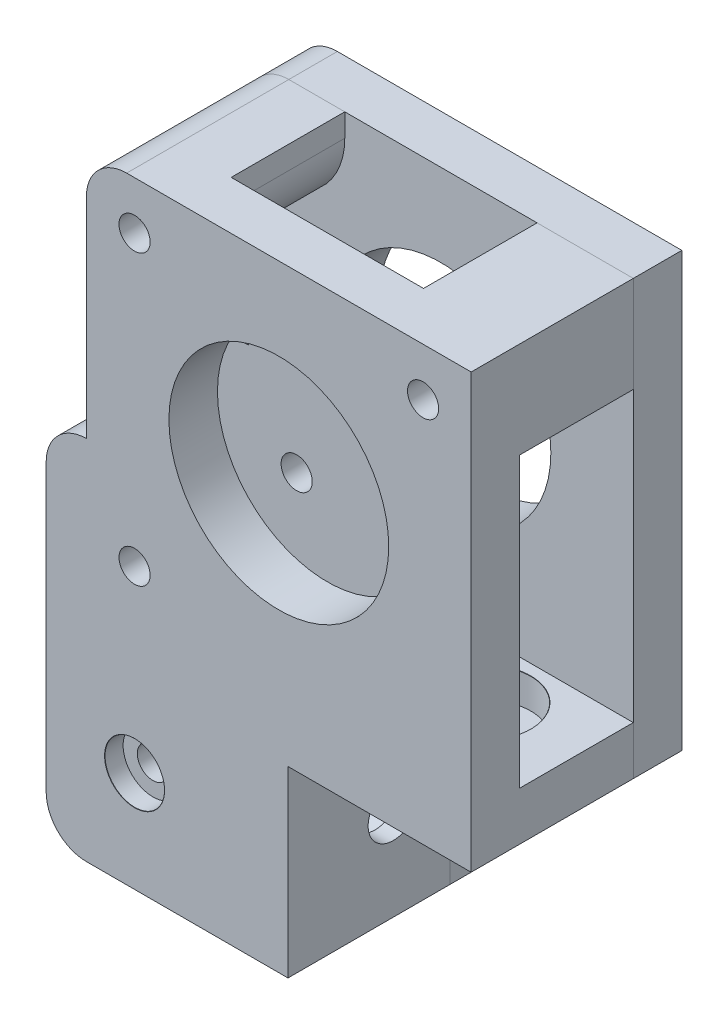
SolidWorks part; units mm, degrees
ref_plane "Front Plane" through (0, 0, 0) normal (0, 0, 1) x (1, 0, 0)
ref_plane "Top Plane" through (0, 0, 0) normal (0, 1, 0) x (1, 0, 0)
ref_plane "Right Plane" through (0, 0, 0) normal (1, 0, 0) x (0, 0, -1)
sketch "Sketch16" plane through (0, 0, 0) normal (0, 0, 1) x (1, 0, 0)
  line L1 (-21, 21) -> (21, 21)
  line L2 (-21, 21) -> (-21, -21)
  line L3 (-21, -21) -> (21, -21)
  line L4 (21, 21) -> (21, -21)
  line L5 (-21, 21) -> (21, -21) construction
  line L6 (-21, -21) -> (21, 21) construction
  point P0 (0, 0)
  dimension "D1" = 42
  dimension "D2" = 42
extrude "Boss-Extrude4" add sketch "Sketch16" against normal blind 5.3
sketch "Sketch19" plane through (0, 0, 0) normal (0, 0, 1) x (1, 0, 0)
  line L0 (21, -21) -> (21, -26.3)
  line L1 (21, -26.3) -> (1, -26.3)
  line L2 (1, -26.3) -> (1, -21)
  line L3 (-21, -21) -> (21, -21) construction
  line L4 (1, -21) -> (21, -21)
  dimension "D1" = 5.3
  dimension "D2" = 20
extrude "Boss-Extrude7" add sketch "Sketch19" against normal blind 23
sketch "Sketch20" plane through (0, 0, 0) normal (0, 0, 1) x (1, 0, 0)
  line L0 (1, -21) -> (-4.3, -21)
  line L1 (-21, -21) -> (1, -21) construction
  line L2 (-4.3, -21) -> (-4.3, -46.3)
  line L3 (-4.3, -46.3) -> (1, -46.3)
  line L4 (1, -46.3) -> (1, -21)
  dimension "D1" = 25.3
  dimension "D2" = 5.3
extrude "Boss-Extrude8" add sketch "Sketch20" against normal blind 23
sketch "Sketch21" plane through (0, -21, 0) normal (0, -1, 0) x (1, 0, 0)
  line L1 (-21, -5.3) -> (-4.3, -5.3)
  line L2 (-21, -5.3) -> (-21, 0)
  line L3 (-21, 0) -> (-4.3, 0)
  line L4 (-4.3, -5.3) -> (-4.3, 0)
extrude "Boss-Extrude9" add sketch "Sketch21" along normal up to surface (25.3 mm away) up to face at (-1.65, -46.3, -11.5)
sketch "Sketch22" plane through (0, 0, -23) normal (0, 0, -1) x (-1, 0, 0)
  line L0 (-21, -21) -> (-21, 21)
  line L1 (-21, 21) -> (21, 21)
  line L2 (21, 21) -> (21, -46.3)
  line L3 (21, -46.3) -> (4.3, -46.3)
  line L4 (4.3, -46.3) -> (4.3, -21)
  line L5 (4.3, -21) -> (-21, -21)
extrude "Boss-Extrude10" add sketch "Sketch22" against normal blind 5.3
sketch "Sketch23" plane through (-4.3, 0, 0) normal (-1, 0, 0) x (0, 0, 1)
  line L0 (-5.3, -46.3) -> (-5.3, -21) construction
  line L1 (-17.7, -46.3) -> (-5.3, -46.3) construction
  point P0 (-11.5, -36.3)
  dimension "D1" = 6.2
  dimension "D2" = 10
sketch "Sketch24" plane through (0, -21, 0) normal (0, 1, 0) x (1, 0, 0)
  line L0 (-21, 17.7) -> (21, 17.7) construction
  line L1 (21, 17.7) -> (21, 5.3) construction
  point P0 (11, 11.5)
  dimension "D1" = 6.2
  dimension "D2" = 10
hole_wizard "CBORE for M5 Cheese Head Screw1" positions "3DSketch1" profile "Sketch25" counterbore size "M5" standard "ISO" end condition up to next
sketch3d "3DSketch1"
  point P0 (11, -21, -11.5)
  point P3 (-4.3, -36.3, -11.5)
sketch "Sketch25" plane through (11, -21, -11.5) normal (1, 0, 0) x (0, 0, 1)
  line L0 (0, 0) -> (0, 5.3)
  line L1 (0, 5.3) -> (2.75, 5.3)
  line L3 (2.75, 5.3) -> (2.75, 3.3)
  line L4 (5, 3.3) -> (2.75, 3.3)
  line L5 (5, 3.3) -> (5, 0.025)
  line L6 (5, 0.025) -> (5.025, 0)
  line L7 (5.025, 0) -> (0, 0)
  line L8 (-5, 0.025) -> (-5.025, 0) construction
  line L11 (0, -6.35) -> (0, 107.95) construction
  dimension "Thru Hole Dia." = 5.5
  dimension "Thru Hole Depth" = 5.3
  dimension "C'Bore Dia." = 10
  dimension "C'Bore Depth" = 3.3
  dimension "Near C'Sink Dia." = 10.05
  dimension "Near C'Sink Angle" = 90
sketch "Sketch27" plane through (0, 0, -5.3) normal (0, 0, -1) x (-1, 0, 0)
  line L1 (10.5, 10.5) -> (21, 10.5)
  line L2 (10.5, 10.5) -> (10.5, 21)
  line L3 (10.5, 21) -> (21, 21)
  line L4 (21, 10.5) -> (21, 21)
  line L5 (10.5, 10.5) -> (21, 21) construction
  line L6 (10.5, 21) -> (21, 10.5) construction
  line L7 (-10.5, 10.5) -> (-21, 10.5)
  line L8 (-10.5, 10.5) -> (-10.5, 21)
  line L9 (-10.5, 21) -> (-21, 21)
  line L10 (-21, 10.5) -> (-21, 21)
  line L11 (-10.5, 10.5) -> (-21, 21) construction
  line L12 (-10.5, 21) -> (-21, 10.5) construction
  point P0 (15.75, 15.75)
  point P7 (-15.75, 15.75)
extrude "Boss-Extrude11" add sketch "Sketch27" along normal up to surface (12.4 mm away) up to face at (-1.4333, -15.4333, -17.7)
sketch "Sketch29" plane through (0, -46.3, 0) normal (0, -1, 0) x (1, 0, 0)
  line L0 (-21, -5.3) -> (-4.3, -5.3) construction
  line L1 (-21, 0) -> (-25.4, 0)
  line L2 (-21, 0) -> (-21, -5.3)
  line L3 (-21, -5.3) -> (-25.4, -5.3)
  line L4 (-25.4, 0) -> (-25.4, -5.3)
  line L5 (-21, -23) -> (1, -23) construction
  line L6 (-21, -17.7) -> (-25.4, -17.7)
  line L7 (-21, -17.7) -> (-21, -23)
  line L8 (-21, -23) -> (-25.4, -23)
  line L9 (-25.4, -17.7) -> (-25.4, -23)
  dimension "D1" = 4.4
extrude "Boss-Extrude12" add sketch "Sketch29" against normal blind 40
sketch "Sketch31" plane through (0, 0, 0) normal (0, 0, 1) x (1, 0, 0)
  line L4 (-25.4, -6.3) -> (-25.4, -46.3) construction
  line L5 (-25.4, -46.3) -> (1, -46.3) construction
  point P0 (-15.75, -35.3)
  dimension "D1" = 9.65
  dimension "D2" = 11
sketch "Sketch35" plane through (0, 0, -23) normal (0, 0, -1) x (-1, 0, 0)
  line L0 (21, -6.3) -> (21, 21) construction
  line L1 (21, 21) -> (-21, 21) construction
  line L2 (-21, -26.3) -> (-21, 21) construction
  point P0 (15.75, 15.75)
  point P1 (-15.75, 15.75)
  point P8 (15.75, -15.75)
  dimension "D1" = 5.25
  dimension "D2" = 5.25
  dimension "D3" = 5.25
  dimension "D4" = 5.25
  dimension "D5" = 5.25
  dimension "D6" = 5.25
sketch "Sketch38" plane through (0, 0, -23) normal (0, 0, -1) x (-1, 0, 0)
  circle A0 centre (15.75, -35.3) radius 2
  dimension "D1" = 4
extrude "Cut-Extrude2" cut sketch "Sketch38" against normal up to next
sketch "Sketch39" plane through (0, 0, -23) normal (0, 0, -1) x (-1, 0, 0)
  line L0 (-21, -26.3) -> (-21, 21) construction
  line L1 (21, 21) -> (-21, 21) construction
  circle A0 centre (0, 0) radius 12
  point P0 (0, 0)
  dimension "D3" = 24
  dimension "D1" = 21
  dimension "D2" = 21
extrude "Cut-Extrude3" cut sketch "Sketch39" against normal through all and the other way through all
fillet "Fillet1" radius 10 1 edges at (-4.3, -21, -11.5)
fillet "Fillet2" radius 8 1 edges at (-10.5, 10.5, -11.5)
fillet "Fillet3" radius 8 1 edges at (10.5, 10.5, -11.5)
fillet "Fillet4" radius 4.39 1 edges at (-25.4, -6.3, -2.65)
fillet "Fillet5" radius 4.39 1 edges at (-25.4, -46.3, -2.65)
fillet "Fillet6" radius 4.39 1 edges at (-25.4, -6.3, -20.35)
fillet "Fillet7" radius 4.39 1 edges at (-25.4, -46.3, -20.35)
fillet "Fillet8" radius 4.39 1 edges at (-21, 21, -11.5)
ref_plane "Plane3" through (0, 0, -17.7) normal (0, 0, 1) x (1, 0, 0)
split "Split1" trim tools "Plane3" bodies to split 160 resulting bodies 161 162
sketch "Sketch41" plane through (0, 0, -5.3) normal (0, 0, -1) x (-1, 0, 0)
  circle A0 centre (15.75, -35.3) radius 4
  circle A1 centre (15.75, -15.75) radius 4
  dimension "D1" = 8
extrude "Boss-Extrude13" add sketch "Sketch41" along normal blind 2
fillet "Fillet9" radius 4.39 2 edges at (-11.75, -15.75, -5.3) (-11.75, -35.3, -5.3)
hole_wizard "CBORE for M3 Cheese Head Screw3" positions "3DSketch9" profile "Sketch37" counterbore size "M3" standard "ISO" end condition through all
sketch3d "3DSketch9"
  point P0 (-15.75, -15.75, -23)
  point P3 (-15.75, 15.75, -23)
  point P6 (15.75, 15.75, -23)
sketch "Sketch37" plane through (-15.75, -15.75, -23) normal (1, 0, 0) x (0, 1, 0)
  line L0 (0, 0) -> (0, 23)
  line L1 (0, 23) -> (1.7, 23)
  line L3 (1.7, 23) -> (1.7, 2)
  line L4 (3.25, 2) -> (1.7, 2)
  line L5 (3.25, 2) -> (3.25, 0.025)
  line L6 (3.25, 0.025) -> (3.275, 0)
  line L7 (3.275, 0) -> (0, 0)
  line L8 (-3.25, 0.025) -> (-3.275, 0) construction
  line L11 (0, -6.35) -> (0, 107.95) construction
  dimension "Thru Hole Dia." = 3.4
  dimension "Thru Hole Depth" = 23
  dimension "C'Bore Dia." = 6.5
  dimension "C'Bore Depth" = 2
  dimension "Near C'Sink Dia." = 6.55
  dimension "Near C'Sink Angle" = 90
hole_wizard "CBORE for M3 Cheese Head Screw1" positions "3DSketch7" profile "Sketch34" counterbore size "M3" standard "ISO" end condition through all
sketch3d "3DSketch7"
  point P0 (-15.75, -35.3, 0)
sketch "Sketch34" plane through (-15.75, -35.3, 0) normal (1, 0, 0) x (0, -1, 0)
  line L0 (0, 0) -> (0, 23)
  line L1 (0, 23) -> (1.7, 23)
  line L3 (1.7, 23) -> (1.7, 2)
  line L4 (3.25, 2) -> (1.7, 2)
  line L5 (3.25, 2) -> (3.25, 0.025)
  line L6 (3.25, 0.025) -> (3.275, 0)
  line L7 (3.275, 0) -> (0, 0)
  line L8 (-3.25, 0.025) -> (-3.275, 0) construction
  line L11 (0, -6.35) -> (0, 107.95) construction
  dimension "Thru Hole Dia." = 3.4
  dimension "Thru Hole Depth" = 23
  dimension "C'Bore Dia." = 6.5
  dimension "C'Bore Depth" = 2
  dimension "Near C'Sink Dia." = 6.55
  dimension "Near C'Sink Angle" = 90
mirror "Mirror1" [suppressed]
delete or keep bodies "Body-Delete/Keep 1" [suppressed] type delete bodies bodies 158 156
